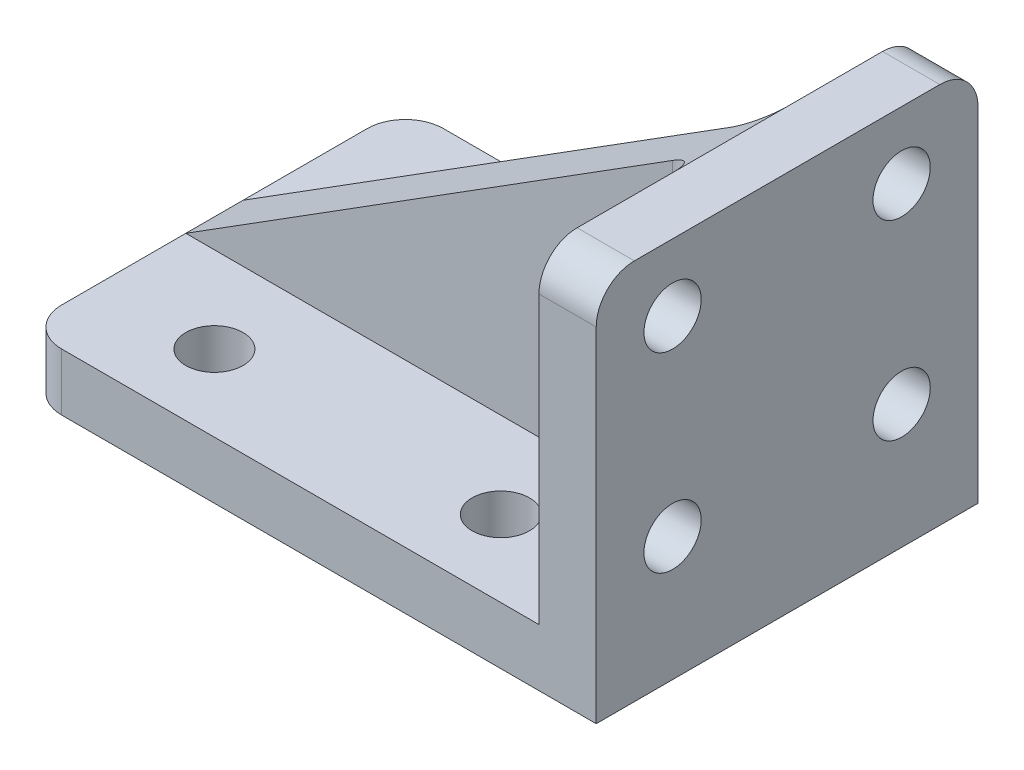
SolidWorks part; units mm, degrees
material "6061 合金"
ref_plane "前视基准面" through (0, 0, 0) normal (0, 0, 1) x (1, 0, 0)
ref_plane "上视基准面" through (0, 0, 0) normal (0, 1, 0) x (1, 0, 0)
ref_plane "右视基准面" through (0, 0, 0) normal (1, 0, 0) x (0, 0, -1)
sketch "草图1" plane through (0, 0, 0) normal (0, 1, 0) x (1, 0, 0)
  line L1 (0, 0) -> (30, 0)
  line L2 (0, 0) -> (0, 20)
  line L3 (0, 20) -> (30, 20)
  line L4 (30, 0) -> (30, 20)
  dimension "D1" = 30
  dimension "D2" = 20
extrude "凸台-拉伸1" add sketch "草图1" along normal blind 3
sketch "草图2" plane through (30, 0, 0) normal (1, 0, 0) x (0, 0, -1)
  line L0 (20, 3) -> (20, 0) construction
  line L1 (0, 3) -> (20, 3)
  line L2 (0, 3) -> (0, 20)
  line L3 (0, 20) -> (20, 20)
  line L4 (20, 3) -> (20, 20)
  point P5 (20, 3)
  dimension "D1" = 17
extrude "凸台-拉伸2" add sketch "草图2" against normal blind 3
ref_plane "基准面1" through (0, 0, -10) normal (0, 0, 1) x (1, 0, 0)
sketch "草图3" plane through (0, 0, -10) normal (0, 0, 1) x (1, 0, 0)
  line L0 (27, 20) -> (0, 3)
  line L1 (0, 3) -> (27, 3)
  line L2 (27, 3) -> (27, 20)
extrude "凸台-拉伸3" add sketch "草图3" along normal blind 1.5 and the other way blind 1.5
sketch "草图4" plane through (0, 3, 0) normal (0, 1, 0) x (1, 0, 0)
  line L0 (13.5, 20) -> (13.5, 11.5) construction
  line L1 (27, 20) -> (0, 20) construction
  line L2 (0, 11.5) -> (27, 11.5) construction
  line L3 (0, 10) -> (27, 10) construction
  line L4 (0, 11.5) -> (0, 8.5) construction
  line L5 (27, 11.5) -> (27, 8.5) construction
  circle A0 centre (6, 16) radius 1.5
  circle A1 centre (21, 16) radius 1.5
  circle A2 centre (21, 4) radius 1.5
  circle A3 centre (6, 4) radius 1.5
  dimension "D1" = 3
  dimension "D2" = 12
  dimension "D3" = 15
extrude "切除-拉伸1" cut sketch "草图4" against normal through all
sketch "草图5" plane through (27, 0, 0) normal (-1, 0, 0) x (0, 0, 1)
  line L0 (-10, 20) -> (-10, 3) construction
  line L1 (-11.5, 20) -> (-8.5, 20) construction
  line L2 (-11.5, 3) -> (-8.5, 3) construction
  line L3 (-20, 11.5) -> (0, 11.5) construction
  line L4 (-20, 3) -> (-20, 20) construction
  line L5 (0, 20) -> (0, 3) construction
  circle A0 centre (-16, 16.5) radius 1.5
  circle A1 centre (-16, 6.5) radius 1.5
  circle A2 centre (-4, 6.5) radius 1.5
  circle A3 centre (-4, 16.5) radius 1.5
  dimension "D1" = 3
  dimension "D2" = 12
  dimension "D3" = 10
extrude "切除-拉伸2" cut sketch "草图5" against normal through all
fillet "圆角1" radius 1.5 2 edges at (27, 11.5, -8.5) (27, 11.5, -11.5)
fillet "圆角2" radius 2 4 edges at (28.5, 20, -20) (28.5, 20, 0) (0, 1.5, -20) (0, 1.5, 0)
